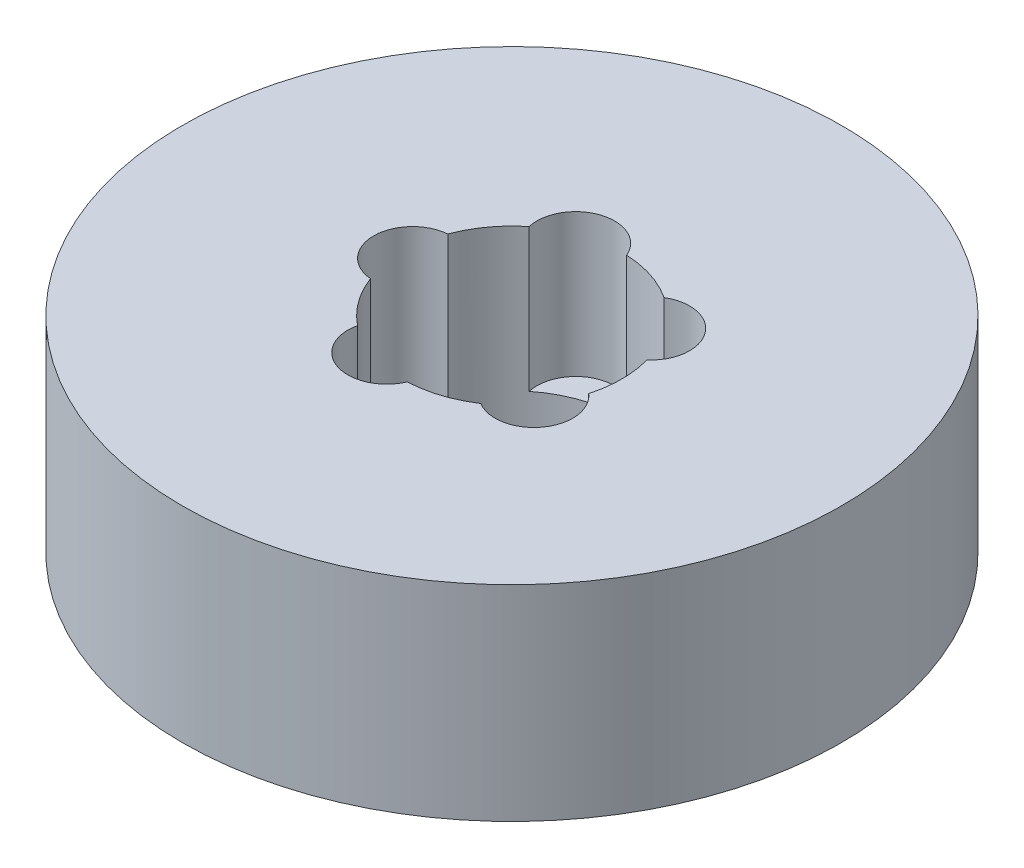
SolidWorks part; units mm, degrees
ref_plane "Front Plane" through (0, 0, 0) normal (0, 0, 1) x (1, 0, 0)
ref_plane "Top Plane" through (0, 0, 0) normal (0, 1, 0) x (1, 0, 0)
ref_plane "Right Plane" through (0, 0, 0) normal (1, 0, 0) x (0, 0, -1)
sketch "Sketch1" plane through (0, 0, 0) normal (0, 1, 0) x (1, 0, 0)
  circle A0 centre (0, 0) radius 22.5
  dimension "FLANGE_OD" = 45
extrude "Boss-Extrude1" add sketch "Sketch1" along normal blind 14
sketch "Sketch2" plane through (0, 0, 0) normal (0, 1, 0) x (1, 0, 0)
  circle A0 centre (0, 0) radius 7.5
  dimension "BORE_D" = 15
extrude "Cut-Extrude1" cut sketch "Sketch2" along normal through all
sketch "Sketch3" plane through (0, 14, 0) normal (0, 1, 0) x (1, 0, 0)
  circle A0 centre (0, 0) radius 6.7864 construction
  circle A1 centre (-6.7864, 0) radius 2.6525
  dimension "BOLT_D" = 5.3049
  dimension "BOLT_PCD" = 13.5728
extrude "Cut-Extrude2" cut sketch "Sketch3" against normal blind 9.7477
pattern_circular "CirPattern1" count 5 over 360 about axis through (0, 0, 0) along (0, 1, 0) of "Cut-Extrude2"
